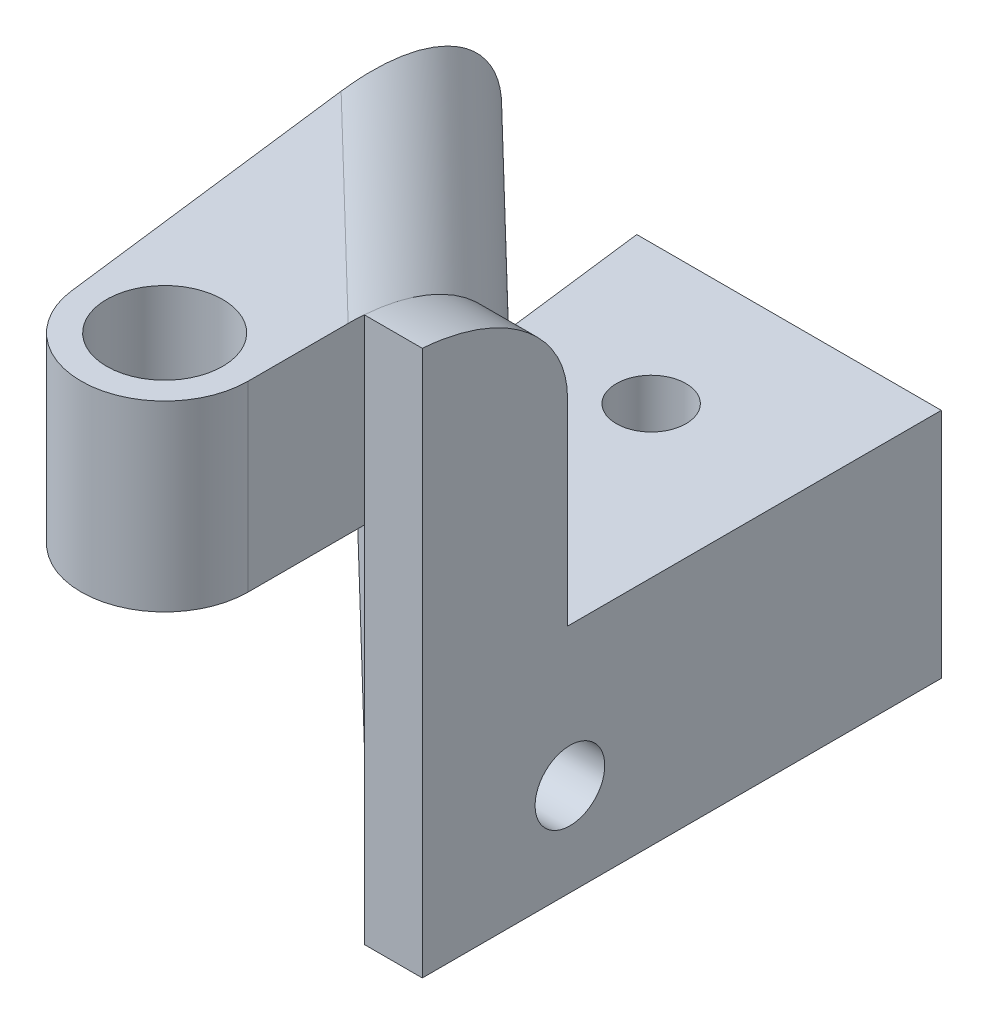
SolidWorks part; units mm, degrees
note: The reader was unsure of these and kept them because the rebuilt part matched: shared geometry of "Croquis1<3>", "Croquis1<6>".
ref_plane "Front Plane" through (0, 0, 0) normal (0, 0, 1) x (1, 0, 0)
ref_plane "Top Plane" through (0, 0, 0) normal (0, 1, 0) x (1, 0, 0)
ref_plane "Right Plane" through (0, 0, 0) normal (1, 0, 0) x (0, 0, -1)
sketch "Croquis1" plane through (0, 0, 0) normal (0, 1, 0) x (1, 0, 0)
  line L5 (-7.02, 27.36) -> (-3.5726, -0.443)
  line L6 (3.6, 0) -> (3.6, 27.36)
  line L7 (3.6, 27.36) -> (-7.02, 27.36)
  line L8 (-5.315, 13.6091) -> (3.6, 5)
  line L9 (0, 0) -> (-2.5, 0) construction
  line L10 (-6.1962, 20.7158) -> (3.6, 11.2557)
  arc A5 (-3.5726, -0.443) -> (3.6, 0) centre (0, 0) ccw
  circle A6 centre (0, 0) radius 2.5
  circle A7 centre (-0.4, 21.36) radius 1.5
  point P13 (0, 0)
  point P14 (0, 0)
  point P16 (-1.71, 22.9676)
  point P17 (0, 0)
  dimension "D1" = 3.6
  dimension "D10" = 3
  dimension "D6" = 5
  dimension "D2" = 10.62
  dimension "D3" = 27.36
  dimension "D4" = 27.803
  dimension "D5" = 27.36
  dimension "D7" = 44
  dimension "D8" = 5
  dimension "D9" = 4.5
  dimension "D11" = 6
  dimension "D12" = 4
extrude "Saliente-Extruir1" add sketch "Croquis1" along normal blind 2.5
extrude "Saliente-Extruir2" add sketch "Croquis1<3>" along normal blind 7.87 from offset 8.15 separate body
sketch "Croquis1<3>" plane through (0, 0, 0) normal (0, 1, 0) x (1, 0, 0) same geometry as "Croquis1"
extrude "Saliente-Extruir5" add sketch "Croquis1<6>" along normal up to surface (16.02 mm away) contours L10 L5 L8 L6 up to face at (0, 16.02, 2.5)
sketch "Croquis1<6>" plane through (0, 0, 0) normal (0, 1, 0) x (1, 0, 0) same geometry as "Croquis1"
fillet "Redondeo3" radius 5 1 edges at (-1.2981, 16.02, -15.9858)
sketch "Croquis8" plane through (3.6, 0, 0) normal (1, 0, 0) x (0, 0, -1)
  line L0 (5, 8.15) -> (5, 15.9949)
  line L1 (5, -7.5) -> (27.36, -7.5)
  line L8 (11.2557, 2.5) -> (11.2557, 11.02)
  line L9 (4.3049, 16.02) -> (0, 16.02)
  line L10 (0, 16.02) -> (0, 8.15)
  line L11 (0, 8.15) -> (5, 8.15)
  line L12 (5, 8.15) -> (5, 0)
  line L13 (5, 0) -> (27.36, 0)
  line L14 (27.36, 0) -> (27.36, 2.5)
  line L15 (27.36, 2.5) -> (11.2557, 2.5)
  line L16 (11.2557, 2.5) -> (11.2557, 11.02)
  line L17 (4.3049, 16.02) -> (0, 16.02)
  line L18 (0, 16.02) -> (0, 8.15)
  line L19 (0, 8.15) -> (5, 8.15)
  line L20 (5, 8.15) -> (5, -7.5)
  line L22 (27.36, -7.5) -> (27.36, 2.5)
  line L23 (27.36, 2.5) -> (11.2557, 2.5)
  circle A0 centre (11.36, -3.5) radius 1.5
  ellipse E1 centre (4.3049, 11.02) end of major axis (-2.6459, 11.02) minor radius 5 (11.2557, 11.02) -> (4.3049, 16.02) ccw
  ellipse E2 centre (4.3049, 11.02) end of major axis (-2.6459, 11.02) minor radius 5 (11.2557, 11.02) -> (4.3049, 16.02) ccw
  point P25 (0, 0)
  point P28 (5.8179, -1.8669)
  line M10 (11.2557, 2.5) -> (11.2557, 11.02)
  ellipse M11 centre (4.3049, 11.02) end of major axis (-2.6459, 11.02) minor radius 5 (11.2557, 11.02) -> (4.3049, 16.02) ccw
  line M15 (5, 8.15) -> (5, 0)
  line M16 (5, 0) -> (27.36, 0)
  line M17 (27.36, 0) -> (27.36, 2.5)
  line M18 (27.36, 2.5) -> (11.2557, 2.5)
  dimension "D3" = 3
  dimension "D2" = 10
  dimension "D4" = 4
  dimension "D5" = 16
  dimension "D1" = 0
extrude "Saliente-Extruir6" add sketch "Croquis8" along normal blind 2.5 contours L1 L22 L20 M16 | L0 M15 M16 M17 M18 M10 M11
